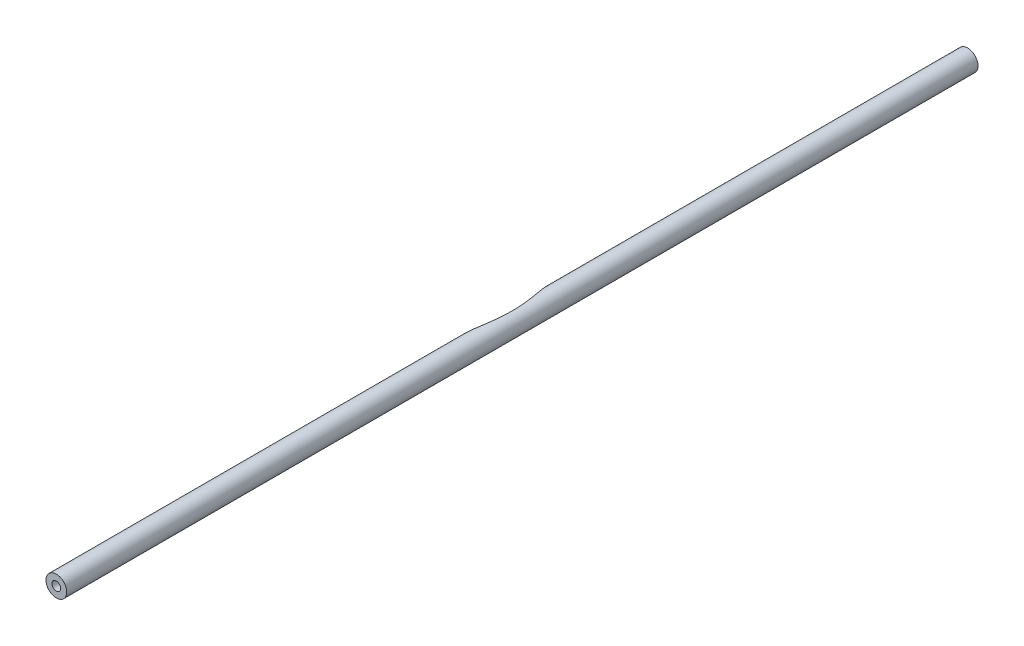
SolidWorks part; units mm, degrees
material "PVC 0.007 Plastificado"
ref_plane "Alzado" through (0, 0, 0) normal (0, 0, 1) x (1, 0, 0)
ref_plane "Planta" through (0, 0, 0) normal (0, 1, 0) x (1, 0, 0)
ref_plane "Vista lateral" through (0, 0, 0) normal (1, 0, 0) x (0, 0, -1)
sketch "Croquis1" plane through (0, 0, 0) normal (0, 0, 1) x (1, 0, 0)
  circle A0 centre (0, 0) radius 5
  dimension "D1" = 10
extrude "Saliente-Extruir1" add sketch "Croquis1" along normal blind 220 and the other way blind 220
sketch "Croquis3" plane through (0, 0, 220) normal (0, 0, 1) x (1, 0, 0)
  point P0 (0, 0)
hole_wizard "Perforador para roscar para macho de roscar para M5x0.81" positions "Croquis4" profile "Croquis5" hole size "M5x0.8" standard "Ansi Metric"
sketch "Croquis4" plane through (0, 0, 220) normal (0, 0, 1) x (1, 0, 0)
  point P0 (0, 0)
sketch "Croquis5" plane through (0, 0, 220) normal (1, 0, 0) x (0, -1, 0)
  line L0 (0, 0) -> (0, 41.2618)
  line L1 (0, 41.2618) -> (2.1, 40)
  line L2 (2.1, 40) -> (2.1, 0)
  line L5 (2.1, 0) -> (0, 0)
  line L10 (0, 41.2618) -> (-2.1, 40) construction
  line L11 (0, -6.35) -> (0, 107.95) construction
  dimension "Diámetro de taladro" = 4.2
  dimension "Profundidad de taladro" = 40
  dimension "Ángulo de perforador" = 118
mirror "Simetría2" about plane through (0, 0, 0) normal (0, 0, 1) of "Perforador para roscar para macho de roscar para M5x0.81"
sketch "Croquis6" plane through (0, 0, 0) normal (0, 1, 0) x (1, 0, 0)
  circle A0 centre (-58.5102, 0) radius 58.5102
extrude "Cortar-Extruir1" cut sketch "Croquis6" against normal through all both and the other way through all
sketch "Croquis7" plane through (0, 0, 0) normal (0, 1, 0) x (1, 0, 0)
  line L0 (0, 71.3609) -> (0, -66.7384)
